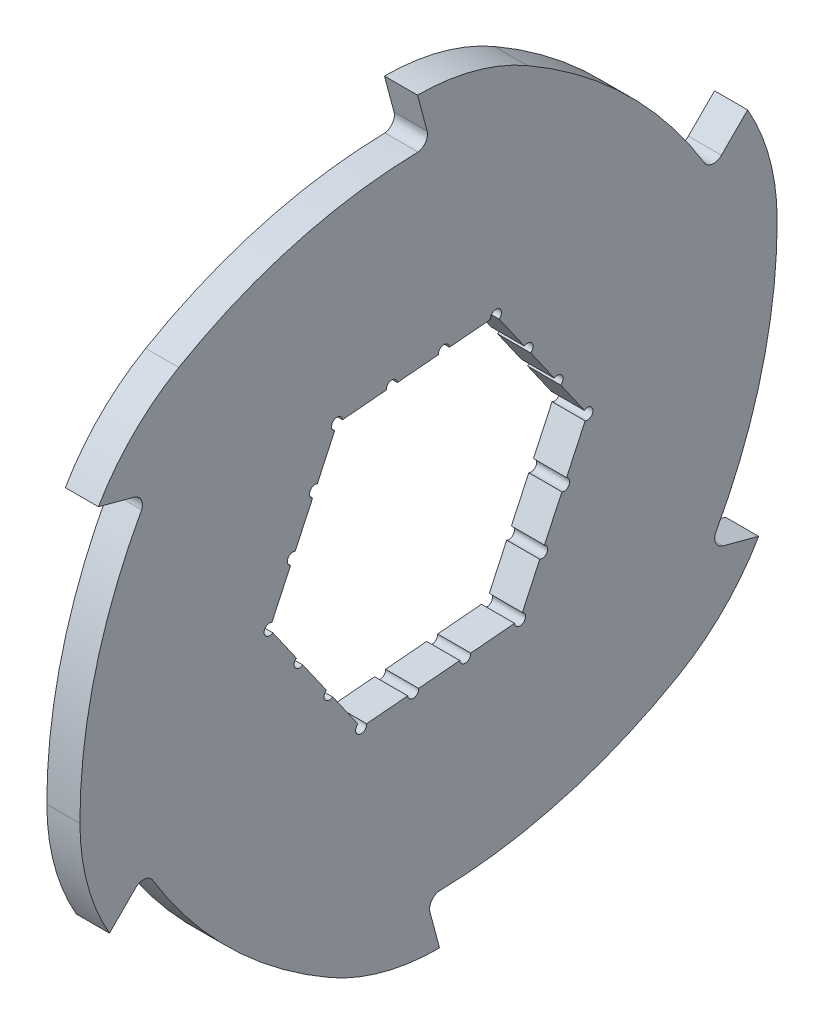
SolidWorks part; units mm, degrees
material "1.0037 (S235JR)"
ref_plane "Alzado" through (0, 0, 0) normal (0, 0, 1) x (1, 0, 0)
ref_plane "Planta" through (0, 0, 0) normal (0, 1, 0) x (1, 0, 0)
ref_plane "Vista lateral" through (0, 0, 0) normal (1, 0, 0) x (0, 0, -1)
sketch "Sketch1" plane through (0, 0, 0) normal (1, 0, 0) x (0, 0, -1)
  line L0 (-56.6126, 0) -> (65.57, 0) construction
  line L1 (28.8152, 2.521) -> (12.2243, 26.2152)
  line L2 (12.2243, 26.2152) -> (-16.5908, 23.6942)
  line L3 (-16.5908, 23.6942) -> (-28.8152, -2.521)
  line L4 (-28.8152, -2.521) -> (-12.2243, -26.2152)
  line L5 (-12.2243, -26.2152) -> (16.5908, -23.6942)
  line L6 (16.5908, -23.6942) -> (28.8152, 2.521)
  circle A0 centre (0, 0) radius 25.05 construction
  circle A1 centre (0, 0) radius 59
  dimension "D2" = 118
  dimension "D1" = 50.1
  dimension "D3" = 55
extrude "Extrude1" add sketch "Sketch1" along normal mid plane 6
ref_axis "Axis1" through (-5.5, 0, 0) along (1, 0, 0)
sketch "Sketch2" plane through (0, 0, 0) normal (1, 0, 0) x (0, 0, -1)
  line L0 (-2, 67.9618) -> (-0.2627, 61.4781)
  line L1 (0, 0) -> (0, 77.6328) construction
  line L4 (-2.1226, 58.9618) -> (0, 0) construction
  circle A0 centre (0, 0) radius 59 construction
  arc A1 (-2, 67.9618) -> (17.9271, 62.6448) centre (-2, 27.9618) cw
  arc A3 (51.2137, 29.2943) -> (-2.1226, 58.9618) centre (0, 0) ccw
  arc A4 (-0.2627, 61.4781) -> (-2.1226, 58.9618) centre (-2.1946, 60.9605) cw
  arc A5 (17.9271, 62.6448) -> (51.2137, 29.2943) centre (-26.9089, -15.3919) cw
  point P10 (-2, 67.9618)
  dimension "D2" = 40
  dimension "D4" = 2
  dimension "D3" = 9
  dimension "D6" = 90
  dimension "D1" = 15
  dimension "D5" = 2
extrude "Extrude2" add sketch "Sketch2" against normal mid plane 6
fillet "Fillet1" [suppressed] radius 0.6
pattern_circular "CirPattern1" count 6 over 360 about axis through (-5.5, 0, 0) along (1, 0, 0) of "Extrude2", "Fillet1"
sketch "Sketch4" [suppressed] plane through (3, 0, 0) normal (1, 0, 0) x (0, 0, -1)
  circle A0 centre (0, 0) radius 67.9646 construction
  dimension "D1" = 135.9291
hole_wizard "Ø2.0 (2) Diameter Hole1" positions "Sketch5" profile "Sketch7" hole size "Ø2.0" standard "ISO" end condition up to next
sketch "Sketch5" plane through (3, 0, 0) normal (1, 0, 0) x (0, 0, -1)
  point P0 (12.2243, 26.2152)
  point P7 (28.8152, 2.521)
  point P8 (16.5908, -23.6942)
  point P9 (-12.2243, -26.2152)
  point P10 (-28.8152, -2.521)
  point P11 (-16.5908, 23.6942)
  dimension "D1" = 6
sketch "Sketch7" plane through (3, 26.2152, -12.2243) normal (0, 1, 0) x (0, 0, -1)
  line L0 (0, 0) -> (0, 6)
  line L1 (0, 6) -> (1, 6)
  line L2 (1, 6) -> (1, 0)
  line L5 (1, 0) -> (0, 0)
  line L11 (0, -6.35) -> (0, 107.95) construction
  dimension "Diámetro de taladro hasta el siguiente" = 2
  dimension "Profundidad de taladro hasta el siguiente" = 6
hole_wizard "Ø2.0 (2) Diameter Hole3" positions "Sketch10" profile "Sketch11" hole size "Ø2.0" standard "ISO" end condition up to next
sketch "Sketch10" plane through (3, 0, 0) normal (1, 0, 0) x (0, 0, -1)
  line L0 (12.7979, 25.396) -> (17.9458, 18.0441) construction
  line L1 (28.2416, 3.3402) -> (12.7979, 25.396) construction
  line L2 (17.9458, 18.0441) -> (23.0937, 10.6921) construction
  line L3 (23.0937, 10.6921) -> (28.2416, 3.3402) construction
  point P2 (17.9458, 18.0441)
sketch "Sketch11" plane through (3, 18.0441, -17.9458) normal (0, 1, 0) x (0, 0, -1)
  line L0 (0, 0) -> (0, 6.001)
  line L1 (0, 6.001) -> (1, 6.001)
  line L2 (1, 6.001) -> (1, 0)
  line L5 (1, 0) -> (0, 0)
  line L11 (0, -6.35) -> (0, 107.95) construction
  dimension "Diámetro de taladro hasta el siguiente" = 2
  dimension "Profundidad de taladro hasta el siguiente" = 6.001
hole_wizard "Ø2.0 (2) Diameter Hole4" positions "Sketch12" profile "Sketch13" hole size "Ø2.0" standard "ISO" end condition up to next
sketch "Sketch12" plane through (3, 0, 0) normal (1, 0, 0) x (0, 0, -1)
  line L0 (28.2416, 3.3402) -> (18.5194, 17.2249) construction
  point P0 (23.3805, 10.2825)
sketch "Sketch13" plane through (3, 10.2825, -23.3805) normal (0, 1, 0) x (0, 0, -1)
  line L0 (0, 0) -> (0, 6.001)
  line L1 (0, 6.001) -> (1, 6.001)
  line L2 (1, 6.001) -> (1, 0)
  line L5 (1, 0) -> (0, 0)
  line L11 (0, -6.35) -> (0, 107.95) construction
  dimension "Diámetro de taladro hasta el siguiente" = 2
  dimension "Profundidad de taladro hasta el siguiente" = 6.001
pattern_circular "CirPattern2" count 6 every 60 about axis through (-5.5, 0, 0) along (1, 0, 0) of "Ø2.0 (2) Diameter Hole3" reverse direction yes
pattern_circular "CirPattern3" count 6 every 60 about axis through (-5.5, 0, 0) along (1, 0, 0) of "Ø2.0 (2) Diameter Hole4"
equation "\"D1@Extrude2\"=\"D1@Extrude1\""
